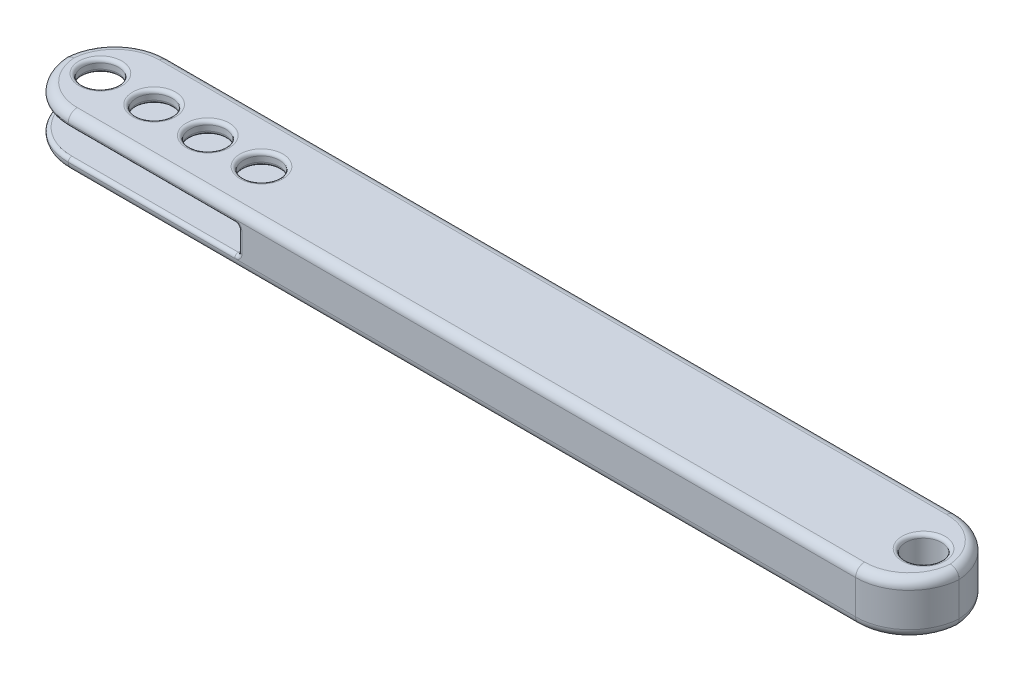
SolidWorks part; units mm, degrees
ref_plane "Front Plane" through (0, 0, 0) normal (0, 0, 1) x (1, 0, 0)
ref_plane "Top Plane" through (0, 0, 0) normal (0, 1, 0) x (1, 0, 0)
ref_plane "Right Plane" through (0, 0, 0) normal (1, 0, 0) x (0, 0, -1)
sketch "Sketch1" plane through (0, 0, 0) normal (0, 1, 0) x (1, 0, 0)
  line L1 (0, 0) -> (100, 0)
  line L2 (0, 0) -> (0, 11.2)
  line L3 (0, 11.2) -> (100, 11.2)
  line L4 (100, 0) -> (100, 11.2)
  line L5 (0, 0) -> (100, 11.2) construction
  line L6 (0, 11.2) -> (100, 0) construction
  point P4 (50, 5.6)
  dimension "D1" = 100
  dimension "D2" = 11.2
extrude "Boss-Extrude1" add sketch "Sketch1" along normal blind 5.8
sketch "Sketch2" plane through (0, 5.8, 0) normal (0, 1, 0) x (1, 0, 0)
  line L0 (0, 5.6) -> (100, 5.6) construction
  line L1 (0, 11.2) -> (0, 0) construction
  line L2 (100, 0) -> (100, 11.2) construction
  circle A0 centre (4, 5.6) radius 2
  circle A1 centre (96, 5.6) radius 2
  circle A2 centre (10, 5.6) radius 2
  circle A3 centre (16, 5.6) radius 2
  circle A4 centre (22, 5.6) radius 2
  dimension "D1" = 4
  dimension "D2" = 4
  dimension "D3" = 4
  dimension "D4" = 4
  dimension "D5" = 4
extrude "Cut-Extrude1" cut sketch "Sketch2" against normal through all
fillet "Fillet1" radius 6 4 edges at (100, 2.9, 0) (100, 2.9, -11.2) (0, 2.9, -11.2) (0, 2.9, 0)
fillet "Fillet2" radius 1 12 edges at (1.9012, 0, -1.6182) (98.0988, 0, -1.6182) (1.9012, 5.8, -1.6182) (98.0988, 5.8, -1.6182) (98.0988, 5.8, -9.5818) (1.9012, 5.8, -9.5818) (98.0988, 0, -9.5818) (1.9012, 0, -9.5818) (50, 0, 0) (50, 5.8, 0) (50, 5.8, -11.2) (50, 0, -11.2)
sketch "Sketch3" plane through (0, 0, -11.2) normal (0, 0, -1) x (-1, 0, 0)
  line L0 (-0.0133, 2.9) -> (-110.1882, 2.9) construction
  line L1 (-0.0133, 1) -> (-0.0133, 4.8) construction
  line L3 (-0.0133, 1.4) -> (-25.0133, 1.4)
  line L4 (-0.0133, 1.4) -> (-0.0133, 4.4)
  line L5 (-0.0133, 4.4) -> (-25.0133, 4.4)
  line L6 (-25.0133, 1.4) -> (-25.0133, 4.4)
  line L7 (-0.0133, 1.4) -> (-25.0133, 4.4) construction
  line L8 (-0.0133, 4.4) -> (-25.0133, 1.4) construction
  point P8 (-12.5133, 2.9)
  dimension "D1" = 25
  dimension "D2" = 3
extrude "Cut-Extrude2" cut sketch "Sketch3" against normal through all
fillet "Fillet3" radius 0.4 30 edges at (1.9012, 4.4, -1.6182) (1.9012, 4.4, -9.5818) (1.9012, 1.4, -1.6182) (1.9012, 1.4, -9.5818) (15.5067, 4.4, 0) (15.5067, 4.4, -11.2) (15.5067, 1.4, 0) (15.5067, 1.4, -11.2) (96, 5.8, -3.6) (96, 0, -3.6) (4, 5.8, -3.6) (2, 4.4, -5.6) (4, 0, -3.6) (6, 1.4, -5.6) (25.0133, 4.4, -5.6) (25.0133, 2.9, 0) (25.0133, 1.4, -5.6) (25.0133, 2.9, -11.2) (22, 0, -3.6) (24, 1.4, -5.6) (22, 5.8, -3.6) (20, 4.4, -5.6) (16, 0, -3.6) (18, 1.4, -5.6) (16, 5.8, -3.6) (14, 4.4, -5.6) (10, 0, -3.6) (12, 1.4, -5.6) (10, 5.8, -3.6) (8, 4.4, -5.6)
